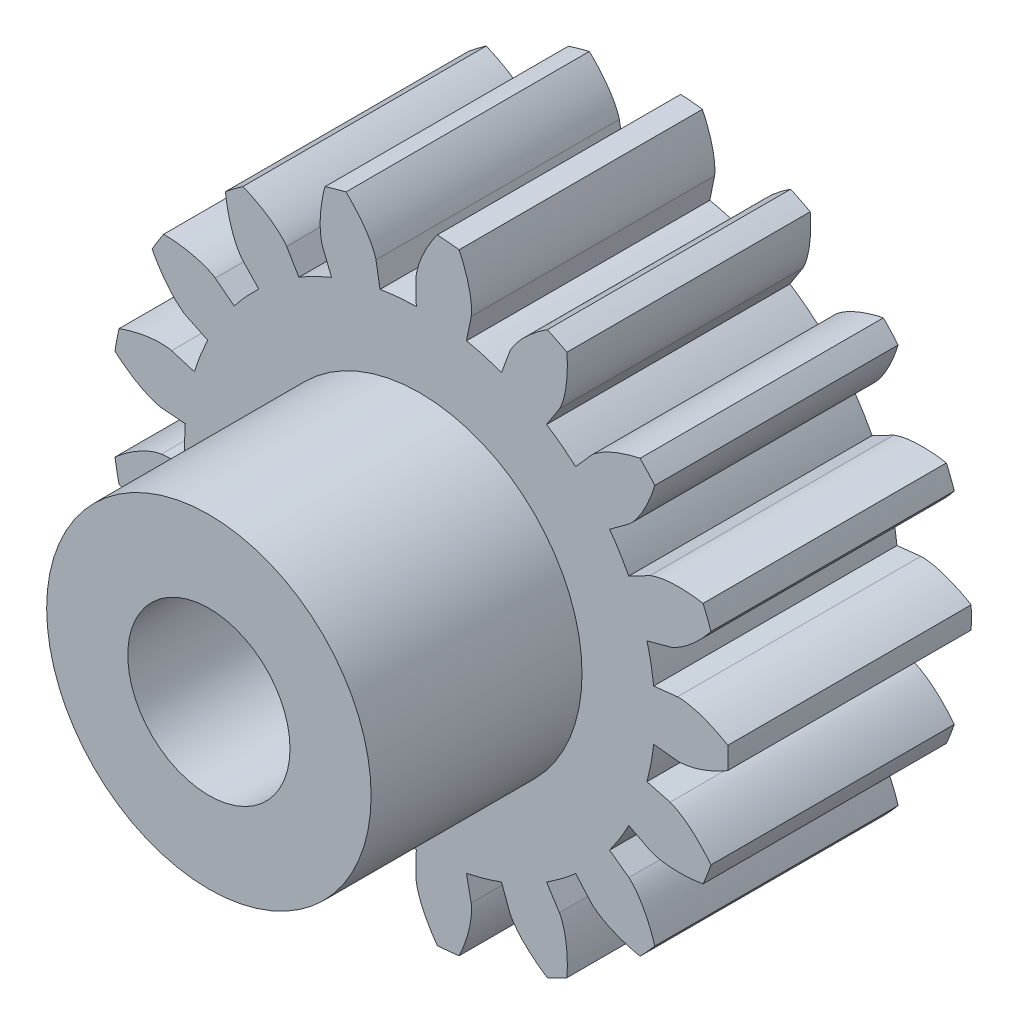
SolidWorks part; units mm, degrees
other "Kamera1"
ref_plane "Płaszczyzna przednia" through (0, 0, 0) normal (0, 0, 1) x (1, 0, 0)
ref_plane "Płaszczyzna górna" through (0, 0, 0) normal (0, 1, 0) x (1, 0, 0)
ref_plane "Płaszczyzna prawa" through (0, 0, 0) normal (1, 0, 0) x (0, 0, -1)
sketch "Szkic1" plane through (0, 0, 0) normal (0, 0, 1) x (1, 0, 0)
  circle A0 centre (0, 0) radius 9.5
extrude "Dodanie-wyciągnięcie1" add sketch "Szkic1" along normal blind 7.5
sketch "Szkic2" plane through (0, 0, 7.5) normal (0, 0, 1) x (1, 0, 0)
  circle A0 centre (0, 0) radius 5
extrude "Dodanie-wyciągnięcie2" add sketch "Szkic2" along normal blind 6.5
sketch "Szkic3" plane through (0, 0, 14) normal (0, 0, 1) x (1, 0, 0)
  circle A0 centre (0, 0) radius 2.5
extrude "Wytnij-wyciągnięcie1" cut sketch "Szkic3" against normal through all
sketch "Szkic5" plane through (0, 0, 0) normal (0, 0, -1) x (-1, 0, 0)
  line L0 (7.9634, 0.6184) -> (7.2282, 0.5613)
  line L1 (7.2282, -0.5613) -> (7.9634, -0.6184)
  line L2 (7.649, -2.3001) -> (6.9429, -2.0878)
  line L3 (6.5374, -3.1345) -> (7.2023, -3.4533)
  line L4 (6.3016, -4.9079) -> (5.7199, -4.4548)
  line L5 (4.9636, -5.2844) -> (5.4684, -5.8219)
  line L6 (4.1031, -6.8529) -> (3.7243, -6.2203)
  line L7 (2.7195, -6.7206) -> (2.9961, -7.4042)
  line L8 (1.3505, -7.8724) -> (1.2258, -7.1456)
  line L9 (0.1081, -7.2492) -> (0.119, -7.9865)
  line L10 (-1.5845, -7.8286) -> (-1.4382, -7.1059)
  line L11 (-2.518, -6.7987) -> (-2.7741, -7.4902)
  line L12 (-4.3056, -6.7276) -> (-3.9081, -6.1065)
  line L13 (-4.8039, -5.43) -> (-5.2925, -5.9823)
  line L14 (-6.4451, -4.7179) -> (-5.8501, -4.2824)
  line L15 (-6.441, -3.328) -> (-7.0962, -3.6665)
  line L16 (-7.7142, -2.0711) -> (-7.002, -1.8799)
  line L17 (-7.2083, -0.7765) -> (-7.9414, -0.8554)
  line L18 (-7.9414, 0.8554) -> (-7.2083, 0.7765)
  line L19 (-7.002, 1.8799) -> (-7.7142, 2.0711)
  line L20 (-7.0962, 3.6665) -> (-6.441, 3.328)
  line L21 (-5.8501, 4.2824) -> (-6.4451, 4.7179)
  line L22 (-5.2925, 5.9823) -> (-4.8039, 5.43)
  line L23 (-3.9081, 6.1065) -> (-4.3056, 6.7276)
  line L24 (-2.7741, 7.4902) -> (-2.518, 6.7987)
  line L25 (-1.4382, 7.1059) -> (-1.5845, 7.8286)
  line L26 (0.119, 7.9865) -> (0.1081, 7.2492)
  line L27 (1.2258, 7.1456) -> (1.3505, 7.8724)
  line L28 (2.9961, 7.4042) -> (2.7195, 6.7206)
  line L29 (3.7243, 6.2203) -> (4.1031, 6.8529)
  line L30 (5.4684, 5.8219) -> (4.9636, 5.2844)
  line L31 (5.7199, 4.4548) -> (6.3016, 4.9079)
  line L32 (7.2023, 3.4533) -> (6.5374, 3.1345)
  line L33 (6.9429, 2.0878) -> (7.649, 2.3001)
  circle A1 centre (0, 0) radius 9.5
  spline S0 degree 4 poles (7.9634, -0.6184) (7.9667, -0.6187) (7.976, -0.6197) (7.9934, -0.6223) (8.0218, -0.6274) (8.0577, -0.6353) (8.1038, -0.647) (8.1577, -0.6627) (8.2166, -0.682) (8.2801, -0.7052) (8.3429, -0.7302) (8.405, -0.757) (8.4665, -0.7852) (8.5402, -0.8212) (8.6279, -0.867) (8.7289, -0.9243) (8.8418, -0.9935) (8.9549, -1.0687) (9.0646, -1.1464) (9.1734, -1.2291) (9.2772, -1.3122) (9.3829, -1.4026) (9.4793, -1.4883) (9.5847, -1.5888) (9.669, -1.6713) (9.7774, -1.7849) (9.8406, -1.8533) (9.9135, -1.9351) (9.9453, -1.9723) (9.9649, -1.9951) knots 0 0 0 0 0 0.005377 0.015084 0.028532 0.04661 0.064855 0.092111 0.119476 0.146842 0.174209 0.201575 0.228941 0.256307 0.307035 0.361767 0.4165 0.471232 0.525964 0.580697 0.635429 0.690161 0.744894 0.799626 0.854358 0.909091 0.954545 1 1 1 1 1 construction
  spline S1 degree 4 poles (7.9634, -0.6184) (7.9667, -0.6187) (7.976, -0.6197) (7.9934, -0.6223) (8.0218, -0.6274) (8.0577, -0.6353) (8.1038, -0.647) (8.1577, -0.6627) (8.2166, -0.682) (8.2801, -0.7052) (8.3429, -0.7302) (8.405, -0.757) (8.4665, -0.7852) (8.5402, -0.8212) (8.6279, -0.867) (8.7289, -0.9243) (8.8418, -0.9935) (8.9549, -1.0687) (9.0646, -1.1464) (9.1734, -1.2291) (9.2772, -1.3122) (9.3829, -1.4026) (9.4793, -1.4883) (9.5847, -1.5888) (9.669, -1.6713) (9.7539, -1.7602) (9.7949, -1.8041) (9.8157, -1.8267) knots 0 0 0 0 0 0.005377 0.015084 0.028532 0.04661 0.064855 0.092111 0.119476 0.146842 0.174209 0.201575 0.228941 0.256307 0.307035 0.361767 0.4165 0.471232 0.525964 0.580697 0.635429 0.690161 0.744894 0.799626 0.854358 0.909091 0.909091 0.909091 0.909091 0.909091
  spline S2 degree 4 poles (7.9634, 0.6184) (7.9667, 0.6187) (7.976, 0.6197) (7.9934, 0.6223) (8.0218, 0.6274) (8.0577, 0.6353) (8.1038, 0.647) (8.1577, 0.6627) (8.2166, 0.682) (8.2801, 0.7052) (8.3429, 0.7302) (8.405, 0.757) (8.4665, 0.7852) (8.5402, 0.8212) (8.6279, 0.867) (8.7289, 0.9243) (8.8418, 0.9935) (8.9549, 1.0687) (9.0646, 1.1464) (9.1734, 1.2291) (9.2772, 1.3122) (9.3829, 1.4026) (9.4793, 1.4883) (9.5847, 1.5888) (9.669, 1.6713) (9.7774, 1.7849) (9.8406, 1.8533) (9.9135, 1.9351) (9.9453, 1.9723) (9.9649, 1.9951) knots 0 0 0 0 0 0.005377 0.015084 0.028532 0.04661 0.064855 0.092111 0.119476 0.146842 0.174209 0.201575 0.228941 0.256307 0.307035 0.361767 0.4165 0.471232 0.525964 0.580697 0.635429 0.690161 0.744894 0.799626 0.854358 0.909091 0.954545 1 1 1 1 1 construction
  spline S3 degree 4 poles (7.9634, 0.6184) (7.9667, 0.6187) (7.976, 0.6197) (7.9934, 0.6223) (8.0218, 0.6274) (8.0577, 0.6353) (8.1038, 0.647) (8.1577, 0.6627) (8.2166, 0.682) (8.2801, 0.7052) (8.3429, 0.7302) (8.405, 0.757) (8.4665, 0.7852) (8.5402, 0.8212) (8.6279, 0.867) (8.7289, 0.9243) (8.8418, 0.9935) (8.9549, 1.0687) (9.0646, 1.1464) (9.1734, 1.2291) (9.2772, 1.3122) (9.3829, 1.4026) (9.4793, 1.4883) (9.5847, 1.5888) (9.669, 1.6713) (9.7539, 1.7602) (9.7949, 1.8041) (9.8157, 1.8267) knots 0 0 0 0 0 0.005377 0.015084 0.028532 0.04661 0.064855 0.092111 0.119476 0.146842 0.174209 0.201575 0.228941 0.256307 0.307035 0.361767 0.4165 0.471232 0.525964 0.580697 0.635429 0.690161 0.744894 0.799626 0.854358 0.909091 0.909091 0.909091 0.909091 0.909091
  spline S4 degree 2 poles (7.2282, 0.5613) (7.2716, -0.0034) (7.2282, -0.5613) knots 0 0 0 0.499734 0.499734 0.499734
  spline S5 degree 2 poles (6.9429, -2.0878) (6.7793, -2.6299) (6.5374, -3.1345) knots 0 0 0 0.499734 0.499734 0.499734
  spline S6 degree 4 poles (7.2023, -3.4533) (7.2053, -3.4548) (7.2135, -3.4591) (7.2288, -3.4678) (7.2534, -3.4829) (7.284, -3.5032) (7.3228, -3.5307) (7.3675, -3.5649) (7.4154, -3.6041) (7.4662, -3.6487) (7.5157, -3.6947) (7.564, -3.7421) (7.6111, -3.7906) (7.6669, -3.8509) (7.732, -3.9252) (7.8056, -4.0151) (7.8858, -4.1205) (7.9641, -4.2314) (8.0383, -4.3435) (8.1099, -4.4599) (8.1767, -4.5749) (8.2426, -4.6974) (8.3015, -4.8121) (8.3635, -4.9439) (8.4124, -5.0513) (8.4724, -5.1963) (8.5066, -5.283) (8.545, -5.3856) (8.5612, -5.4317) (8.5713, -5.4601) knots 0 0 0 0 0 0.005377 0.015084 0.028532 0.04661 0.064855 0.092111 0.119476 0.146842 0.174209 0.201575 0.228941 0.256307 0.307035 0.361767 0.4165 0.471232 0.525964 0.580697 0.635429 0.690161 0.744894 0.799626 0.854358 0.909091 0.954545 1 1 1 1 1 construction
  spline S7 degree 4 poles (7.2023, -3.4533) (7.2053, -3.4548) (7.2135, -3.4591) (7.2288, -3.4678) (7.2534, -3.4829) (7.284, -3.5032) (7.3228, -3.5307) (7.3675, -3.5649) (7.4154, -3.6041) (7.4662, -3.6487) (7.5157, -3.6947) (7.564, -3.7421) (7.6111, -3.7906) (7.6669, -3.8509) (7.732, -3.9252) (7.8056, -4.0151) (7.8858, -4.1205) (7.9641, -4.2314) (8.0383, -4.3435) (8.1099, -4.4599) (8.1767, -4.5749) (8.2426, -4.6974) (8.3015, -4.8121) (8.3635, -4.9439) (8.4124, -5.0513) (8.4594, -5.1649) (8.4818, -5.2206) (8.493, -5.2492) knots 0 0 0 0 0 0.005377 0.015084 0.028532 0.04661 0.064855 0.092111 0.119476 0.146842 0.174209 0.201575 0.228941 0.256307 0.307035 0.361767 0.4165 0.471232 0.525964 0.580697 0.635429 0.690161 0.744894 0.799626 0.854358 0.909091 0.909091 0.909091 0.909091 0.909091
  spline S8 degree 4 poles (7.649, -2.3001) (7.6522, -2.301) (7.6612, -2.3034) (7.6784, -2.3073) (7.7067, -2.3127) (7.743, -2.3184) (7.7903, -2.3241) (7.8463, -2.329) (7.9081, -2.3322) (7.9757, -2.3335) (8.0433, -2.3329) (8.1109, -2.3304) (8.1784, -2.3263) (8.2602, -2.3193) (8.3584, -2.3083) (8.4733, -2.2914) (8.6036, -2.2676) (8.7363, -2.2383) (8.8666, -2.2055) (8.9979, -2.1677) (9.1247, -2.1278) (9.2559, -2.0816) (9.3768, -2.0365) (9.5114, -1.9809) (9.6198, -1.9344) (9.7619, -1.8677) (9.8456, -1.8266) (9.9431, -1.7767) (9.9862, -1.7536) (10.0127, -1.7393) knots 0 0 0 0 0 0.005377 0.015084 0.028532 0.04661 0.064855 0.092111 0.119476 0.146842 0.174209 0.201575 0.228941 0.256307 0.307035 0.361767 0.4165 0.471232 0.525964 0.580697 0.635429 0.690161 0.744894 0.799626 0.854358 0.909091 0.954545 1 1 1 1 1 construction
  spline S9 degree 4 poles (7.649, -2.3001) (7.6522, -2.301) (7.6612, -2.3034) (7.6784, -2.3073) (7.7067, -2.3127) (7.743, -2.3184) (7.7903, -2.3241) (7.8463, -2.329) (7.9081, -2.3322) (7.9757, -2.3335) (8.0433, -2.3329) (8.1109, -2.3304) (8.1784, -2.3263) (8.2602, -2.3193) (8.3584, -2.3083) (8.4733, -2.2914) (8.6036, -2.2676) (8.7363, -2.2383) (8.8666, -2.2055) (8.9979, -2.1677) (9.1247, -2.1278) (9.2559, -2.0816) (9.3768, -2.0365) (9.5114, -1.9809) (9.6198, -1.9344) (9.7311, -1.8822) (9.7852, -1.8561) (9.8128, -1.8425) knots 0 0 0 0 0 0.005377 0.015084 0.028532 0.04661 0.064855 0.092111 0.119476 0.146842 0.174209 0.201575 0.228941 0.256307 0.307035 0.361767 0.4165 0.471232 0.525964 0.580697 0.635429 0.690161 0.744894 0.799626 0.854358 0.909091 0.909091 0.909091 0.909091 0.909091
  spline S10 degree 2 poles (5.7199, -4.4548) (5.3715, -4.9013) (4.9636, -5.2844) knots 0 0 0 0.499734 0.499734 0.499734
  spline S11 degree 4 poles (5.4684, -5.8219) (5.4707, -5.8244) (5.4768, -5.8314) (5.488, -5.845) (5.5055, -5.8679) (5.5267, -5.8979) (5.5529, -5.9376) (5.5822, -5.9856) (5.6127, -6.0395) (5.644, -6.0994) (5.6735, -6.1602) (5.7014, -6.2218) (5.7278, -6.2841) (5.7581, -6.3604) (5.7919, -6.4533) (5.828, -6.5637) (5.8648, -6.6909) (5.8978, -6.8227) (5.9265, -6.954) (5.9511, -7.0884) (5.9719, -7.2197) (5.9891, -7.3577) (6.0026, -7.486) (6.0128, -7.6313) (6.0196, -7.7491) (6.0232, -7.906) (6.0237, -7.9992) (6.0225, -8.1087) (6.0209, -8.1576) (6.02, -8.1877) knots 0 0 0 0 0 0.005377 0.015084 0.028532 0.04661 0.064855 0.092111 0.119476 0.146842 0.174209 0.201575 0.228941 0.256307 0.307035 0.361767 0.4165 0.471232 0.525964 0.580697 0.635429 0.690161 0.744894 0.799626 0.854358 0.909091 0.954545 1 1 1 1 1 construction
  spline S12 degree 4 poles (5.4684, -5.8219) (5.4707, -5.8244) (5.4768, -5.8314) (5.488, -5.845) (5.5055, -5.8679) (5.5267, -5.8979) (5.5529, -5.9376) (5.5822, -5.9856) (5.6127, -6.0395) (5.644, -6.0994) (5.6735, -6.1602) (5.7014, -6.2218) (5.7278, -6.2841) (5.7581, -6.3604) (5.7919, -6.4533) (5.828, -6.5637) (5.8648, -6.6909) (5.8978, -6.8227) (5.9265, -6.954) (5.9511, -7.0884) (5.9719, -7.2197) (5.9891, -7.3577) (6.0026, -7.486) (6.0128, -7.6313) (6.0196, -7.7491) (6.0224, -7.872) (6.0231, -7.932) (6.0233, -7.9627) knots 0 0 0 0 0 0.005377 0.015084 0.028532 0.04661 0.064855 0.092111 0.119476 0.146842 0.174209 0.201575 0.228941 0.256307 0.307035 0.361767 0.4165 0.471232 0.525964 0.580697 0.635429 0.690161 0.744894 0.799626 0.854358 0.909091 0.909091 0.909091 0.909091 0.909091
  spline S13 degree 4 poles (6.3016, -4.9079) (6.3043, -4.9099) (6.3118, -4.9154) (6.3265, -4.9253) (6.3509, -4.9405) (6.3827, -4.9589) (6.4247, -4.9814) (6.4751, -5.0061) (6.5316, -5.0315) (6.5941, -5.0571) (6.6574, -5.0809) (6.7214, -5.103) (6.7858, -5.1235) (6.8646, -5.1466) (6.9602, -5.1718) (7.0734, -5.1976) (7.2035, -5.2224) (7.3377, -5.2431) (7.4711, -5.2596) (7.6073, -5.2717) (7.7399, -5.2803) (7.879, -5.2846) (8.0079, -5.2863) (8.1536, -5.283) (8.2714, -5.2789) (8.428, -5.268) (8.5209, -5.2599) (8.6298, -5.2486) (8.6783, -5.2426) (8.7082, -5.2389) knots 0 0 0 0 0 0.005377 0.015084 0.028532 0.04661 0.064855 0.092111 0.119476 0.146842 0.174209 0.201575 0.228941 0.256307 0.307035 0.361767 0.4165 0.471232 0.525964 0.580697 0.635429 0.690161 0.744894 0.799626 0.854358 0.909091 0.954545 1 1 1 1 1 construction
  spline S14 degree 4 poles (6.3016, -4.9079) (6.3043, -4.9099) (6.3118, -4.9154) (6.3265, -4.9253) (6.3509, -4.9405) (6.3827, -4.9589) (6.4247, -4.9814) (6.4751, -5.0061) (6.5316, -5.0315) (6.5941, -5.0571) (6.6574, -5.0809) (6.7214, -5.103) (6.7858, -5.1235) (6.8646, -5.1466) (6.9602, -5.1718) (7.0734, -5.1976) (7.2035, -5.2224) (7.3377, -5.2431) (7.4711, -5.2596) (7.6073, -5.2717) (7.7399, -5.2803) (7.879, -5.2846) (8.0079, -5.2863) (8.1536, -5.283) (8.2714, -5.2789) (8.3941, -5.2704) (8.4539, -5.2656) (8.4845, -5.2629) knots 0 0 0 0 0 0.005377 0.015084 0.028532 0.04661 0.064855 0.092111 0.119476 0.146842 0.174209 0.201575 0.228941 0.256307 0.307035 0.361767 0.4165 0.471232 0.525964 0.580697 0.635429 0.690161 0.744894 0.799626 0.854358 0.909091 0.909091 0.909091 0.909091 0.909091
  spline S15 degree 2 poles (3.7243, -6.2203) (3.2382, -6.5107) (2.7195, -6.7206) knots 0 0 0 0.499734 0.499734 0.499734
  spline S16 degree 4 poles (2.9961, -7.4042) (2.9973, -7.4073) (3.0005, -7.416) (3.0059, -7.4328) (3.014, -7.4605) (3.0229, -7.4961) (3.033, -7.5426) (3.043, -7.5979) (3.0519, -7.6592) (3.0595, -7.7263) (3.0651, -7.7937) (3.0688, -7.8613) (3.0709, -7.9288) (3.0716, -8.011) (3.0696, -8.1098) (3.0634, -8.2258) (3.0517, -8.3577) (3.0349, -8.4925) (3.0142, -8.6253) (2.9886, -8.7595) (2.9606, -8.8895) (2.9267, -9.0244) (2.893, -9.1489) (2.85, -9.2881) (2.8138, -9.4003) (2.7604, -9.548) (2.7273, -9.635) (2.6866, -9.7367) (2.6675, -9.7818) (2.6558, -9.8095) knots 0 0 0 0 0 0.005377 0.015084 0.028532 0.04661 0.064855 0.092111 0.119476 0.146842 0.174209 0.201575 0.228941 0.256307 0.307035 0.361767 0.4165 0.471232 0.525964 0.580697 0.635429 0.690161 0.744894 0.799626 0.854358 0.909091 0.954545 1 1 1 1 1 construction
  spline S17 degree 4 poles (2.9961, -7.4042) (2.9973, -7.4073) (3.0005, -7.416) (3.0059, -7.4328) (3.014, -7.4605) (3.0229, -7.4961) (3.033, -7.5426) (3.043, -7.5979) (3.0519, -7.6592) (3.0595, -7.7263) (3.0651, -7.7937) (3.0688, -7.8613) (3.0709, -7.9288) (3.0716, -8.011) (3.0696, -8.1098) (3.0634, -8.2258) (3.0517, -8.3577) (3.0349, -8.4925) (3.0142, -8.6253) (2.9886, -8.7595) (2.9606, -8.8895) (2.9267, -9.0244) (2.893, -9.1489) (2.85, -9.2881) (2.8138, -9.4003) (2.772, -9.516) (2.751, -9.5722) (2.74, -9.6009) knots 0 0 0 0 0 0.005377 0.015084 0.028532 0.04661 0.064855 0.092111 0.119476 0.146842 0.174209 0.201575 0.228941 0.256307 0.307035 0.361767 0.4165 0.471232 0.525964 0.580697 0.635429 0.690161 0.744894 0.799626 0.854358 0.909091 0.909091 0.909091 0.909091 0.909091
  spline S18 degree 4 poles (4.1031, -6.8529) (4.1049, -6.8557) (4.1099, -6.8636) (4.12, -6.878) (4.1373, -6.9011) (4.1603, -6.9297) (4.1913, -6.9658) (4.2295, -7.0071) (4.273, -7.0512) (4.322, -7.0977) (4.3724, -7.1427) (4.4241, -7.1865) (4.4767, -7.2289) (4.5419, -7.2789) (4.6219, -7.3369) (4.7182, -7.4018) (4.8305, -7.472) (4.9482, -7.5397) (5.0666, -7.6033) (5.1892, -7.6638) (5.3098, -7.7197) (5.4379, -7.774) (5.5575, -7.8221) (5.6945, -7.8717) (5.8059, -7.9104) (5.9559, -7.9568) (6.0454, -7.9828) (6.151, -8.0116) (6.1985, -8.0235) (6.2277, -8.0309) knots 0 0 0 0 0 0.005377 0.015084 0.028532 0.04661 0.064855 0.092111 0.119476 0.146842 0.174209 0.201575 0.228941 0.256307 0.307035 0.361767 0.4165 0.471232 0.525964 0.580697 0.635429 0.690161 0.744894 0.799626 0.854358 0.909091 0.954545 1 1 1 1 1 construction
  spline S19 degree 4 poles (4.1031, -6.8529) (4.1049, -6.8557) (4.1099, -6.8636) (4.12, -6.878) (4.1373, -6.9011) (4.1603, -6.9297) (4.1913, -6.9658) (4.2295, -7.0071) (4.273, -7.0512) (4.322, -7.0977) (4.3724, -7.1427) (4.4241, -7.1865) (4.4767, -7.2289) (4.5419, -7.2789) (4.6219, -7.3369) (4.7182, -7.4018) (4.8305, -7.472) (4.9482, -7.5397) (5.0666, -7.6033) (5.1892, -7.6638) (5.3098, -7.7197) (5.4379, -7.774) (5.5575, -7.8221) (5.6945, -7.8717) (5.8059, -7.9104) (5.9234, -7.9468) (5.9809, -7.9639) (6.0104, -7.9724) knots 0 0 0 0 0 0.005377 0.015084 0.028532 0.04661 0.064855 0.092111 0.119476 0.146842 0.174209 0.201575 0.228941 0.256307 0.307035 0.361767 0.4165 0.471232 0.525964 0.580697 0.635429 0.690161 0.744894 0.799626 0.854358 0.909091 0.909091 0.909091 0.909091 0.909091
  spline S20 degree 2 poles (1.2258, -7.1456) (0.6676, -7.2409) (0.1081, -7.2492) knots 0 0 0 0.499734 0.499734 0.499734
  spline S21 degree 4 poles (0.119, -7.9865) (0.119, -7.9898) (0.1189, -7.9991) (0.1179, -8.0167) (0.1154, -8.0454) (0.1109, -8.0819) (0.1035, -8.1289) (0.0928, -8.1841) (0.079, -8.2445) (0.0618, -8.3098) (0.0427, -8.3747) (0.0218, -8.439) (-0.0007, -8.5028) (-0.0297, -8.5796) (-0.0673, -8.671) (-0.1149, -8.7769) (-0.1735, -8.8957) (-0.2379, -9.0153) (-0.3051, -9.1317) (-0.3775, -9.2476) (-0.4506, -9.3587) (-0.5309, -9.4722) (-0.6073, -9.5761) (-0.6977, -9.6904) (-0.772, -9.782) (-0.8751, -9.9004) (-0.9375, -9.9696) (-1.0121, -10.0497) (-1.0462, -10.0848) (-1.0672, -10.1065) knots 0 0 0 0 0 0.005377 0.015084 0.028532 0.04661 0.064855 0.092111 0.119476 0.146842 0.174209 0.201575 0.228941 0.256307 0.307035 0.361767 0.4165 0.471232 0.525964 0.580697 0.635429 0.690161 0.744894 0.799626 0.854358 0.909091 0.954545 1 1 1 1 1 construction
  spline S22 degree 4 poles (0.119, -7.9865) (0.119, -7.9898) (0.1189, -7.9991) (0.1179, -8.0167) (0.1154, -8.0454) (0.1109, -8.0819) (0.1035, -8.1289) (0.0928, -8.1841) (0.079, -8.2445) (0.0618, -8.3098) (0.0427, -8.3747) (0.0218, -8.439) (-0.0007, -8.5028) (-0.0297, -8.5796) (-0.0673, -8.671) (-0.1149, -8.7769) (-0.1735, -8.8957) (-0.2379, -9.0153) (-0.3051, -9.1317) (-0.3775, -9.2476) (-0.4506, -9.3587) (-0.5309, -9.4722) (-0.6073, -9.5761) (-0.6977, -9.6904) (-0.772, -9.782) (-0.8527, -9.8747) (-0.8926, -9.9196) (-0.9132, -9.9424) knots 0 0 0 0 0 0.005377 0.015084 0.028532 0.04661 0.064855 0.092111 0.119476 0.146842 0.174209 0.201575 0.228941 0.256307 0.307035 0.361767 0.4165 0.471232 0.525964 0.580697 0.635429 0.690161 0.744894 0.799626 0.854358 0.909091 0.909091 0.909091 0.909091 0.909091
  spline S23 degree 4 poles (1.3505, -7.8724) (1.3511, -7.8757) (1.353, -7.8848) (1.3572, -7.9019) (1.3649, -7.9296) (1.3761, -7.9647) (1.392, -8.0095) (1.4126, -8.0618) (1.4372, -8.1186) (1.4662, -8.1797) (1.4969, -8.2399) (1.5293, -8.2993) (1.563, -8.3579) (1.6057, -8.428) (1.6594, -8.511) (1.7257, -8.6064) (1.8051, -8.7124) (1.8904, -8.8181) (1.9779, -8.9201) (2.0703, -9.0208) (2.1626, -9.1166) (2.2624, -9.2134) (2.3566, -9.3015) (2.4664, -9.3972) (2.5563, -9.4736) (2.6794, -9.571) (2.7534, -9.6276) (2.8415, -9.6926) (2.8815, -9.7209) (2.906, -9.7383) knots 0 0 0 0 0 0.005377 0.015084 0.028532 0.04661 0.064855 0.092111 0.119476 0.146842 0.174209 0.201575 0.228941 0.256307 0.307035 0.361767 0.4165 0.471232 0.525964 0.580697 0.635429 0.690161 0.744894 0.799626 0.854358 0.909091 0.954545 1 1 1 1 1 construction
  spline S24 degree 4 poles (1.3505, -7.8724) (1.3511, -7.8757) (1.353, -7.8848) (1.3572, -7.9019) (1.3649, -7.9296) (1.3761, -7.9647) (1.392, -8.0095) (1.4126, -8.0618) (1.4372, -8.1186) (1.4662, -8.1797) (1.4969, -8.2399) (1.5293, -8.2993) (1.563, -8.3579) (1.6057, -8.428) (1.6594, -8.511) (1.7257, -8.6064) (1.8051, -8.7124) (1.8904, -8.8181) (1.9779, -8.9201) (2.0703, -9.0208) (2.1626, -9.1166) (2.2624, -9.2134) (2.3566, -9.3015) (2.4664, -9.3972) (2.5563, -9.4736) (2.6527, -9.5499) (2.7001, -9.5867) (2.7246, -9.6053) knots 0 0 0 0 0 0.005377 0.015084 0.028532 0.04661 0.064855 0.092111 0.119476 0.146842 0.174209 0.201575 0.228941 0.256307 0.307035 0.361767 0.4165 0.471232 0.525964 0.580697 0.635429 0.690161 0.744894 0.799626 0.854358 0.909091 0.909091 0.909091 0.909091 0.909091
  spline S25 degree 2 poles (-1.4382, -7.1059) (-1.9932, -6.9931) (-2.518, -6.7987) knots 0 0 0 0.499734 0.499734 0.499734
  spline S26 degree 4 poles (-2.7741, -7.4902) (-2.7753, -7.4933) (-2.7788, -7.5019) (-2.786, -7.518) (-2.7987, -7.5438) (-2.8161, -7.5762) (-2.84, -7.6174) (-2.8699, -7.665) (-2.9046, -7.7163) (-2.9442, -7.771) (-2.9855, -7.8246) (-3.0282, -7.877) (-3.0722, -7.9284) (-3.127, -7.9895) (-3.1951, -8.0612) (-3.2778, -8.1427) (-3.3753, -8.2324) (-3.4785, -8.3206) (-3.5833, -8.4048) (-3.6926, -8.4868) (-3.8009, -8.564) (-3.9168, -8.6408) (-4.0256, -8.7101) (-4.1511, -8.784) (-4.2536, -8.8426) (-4.3924, -8.9157) (-4.4756, -8.9577) (-4.5742, -9.0054) (-4.6186, -9.0259) (-4.646, -9.0385) knots 0 0 0 0 0 0.005377 0.015084 0.028532 0.04661 0.064855 0.092111 0.119476 0.146842 0.174209 0.201575 0.228941 0.256307 0.307035 0.361767 0.4165 0.471232 0.525964 0.580697 0.635429 0.690161 0.744894 0.799626 0.854358 0.909091 0.954545 1 1 1 1 1 construction
  spline S27 degree 4 poles (-2.7741, -7.4902) (-2.7753, -7.4933) (-2.7788, -7.5019) (-2.786, -7.518) (-2.7987, -7.5438) (-2.8161, -7.5762) (-2.84, -7.6174) (-2.8699, -7.665) (-2.9046, -7.7163) (-2.9442, -7.771) (-2.9855, -7.8246) (-3.0282, -7.877) (-3.0722, -7.9284) (-3.127, -7.9895) (-3.1951, -8.0612) (-3.2778, -8.1427) (-3.3753, -8.2324) (-3.4785, -8.3206) (-3.5833, -8.4048) (-3.6926, -8.4868) (-3.8009, -8.564) (-3.9168, -8.6408) (-4.0256, -8.7101) (-4.1511, -8.784) (-4.2536, -8.8426) (-4.3623, -8.8999) (-4.4157, -8.9273) (-4.4432, -8.9411) knots 0 0 0 0 0 0.005377 0.015084 0.028532 0.04661 0.064855 0.092111 0.119476 0.146842 0.174209 0.201575 0.228941 0.256307 0.307035 0.361767 0.4165 0.471232 0.525964 0.580697 0.635429 0.690161 0.744894 0.799626 0.854358 0.909091 0.909091 0.909091 0.909091 0.909091
  spline S28 degree 4 poles (-1.5845, -7.8286) (-1.5851, -7.8319) (-1.5867, -7.8411) (-1.589, -7.8586) (-1.5918, -7.8872) (-1.594, -7.9239) (-1.5954, -7.9715) (-1.5951, -8.0277) (-1.5926, -8.0896) (-1.5877, -8.157) (-1.5808, -8.2242) (-1.5721, -8.2913) (-1.5617, -8.3581) (-1.5473, -8.439) (-1.5272, -8.5358) (-1.4998, -8.6486) (-1.4641, -8.7761) (-1.4227, -8.9055) (-1.378, -9.0323) (-1.3282, -9.1595) (-1.2768, -9.2821) (-1.2187, -9.4085) (-1.1627, -9.5247) (-1.0948, -9.6536) (-1.0386, -9.7573) (-0.959, -9.8926) (-0.9104, -9.9721) (-0.8517, -10.0646) (-0.8247, -10.1054) (-0.8081, -10.1305) knots 0 0 0 0 0 0.005377 0.015084 0.028532 0.04661 0.064855 0.092111 0.119476 0.146842 0.174209 0.201575 0.228941 0.256307 0.307035 0.361767 0.4165 0.471232 0.525964 0.580697 0.635429 0.690161 0.744894 0.799626 0.854358 0.909091 0.954545 1 1 1 1 1 construction
  spline S29 degree 4 poles (-1.5845, -7.8286) (-1.5851, -7.8319) (-1.5867, -7.8411) (-1.589, -7.8586) (-1.5918, -7.8872) (-1.594, -7.9239) (-1.5954, -7.9715) (-1.5951, -8.0277) (-1.5926, -8.0896) (-1.5877, -8.157) (-1.5808, -8.2242) (-1.5721, -8.2913) (-1.5617, -8.3581) (-1.5473, -8.439) (-1.5272, -8.5358) (-1.4998, -8.6486) (-1.4641, -8.7761) (-1.4227, -8.9055) (-1.378, -9.0323) (-1.3282, -9.1595) (-1.2768, -9.2821) (-1.2187, -9.4085) (-1.1627, -9.5247) (-1.0948, -9.6536) (-1.0386, -9.7573) (-0.9763, -9.8633) (-0.9453, -9.9147) (-0.9292, -9.9409) knots 0 0 0 0 0 0.005377 0.015084 0.028532 0.04661 0.064855 0.092111 0.119476 0.146842 0.174209 0.201575 0.228941 0.256307 0.307035 0.361767 0.4165 0.471232 0.525964 0.580697 0.635429 0.690161 0.744894 0.799626 0.854358 0.909091 0.909091 0.909091 0.909091 0.909091
  spline S30 degree 2 poles (-3.9081, -6.1065) (-4.3848, -5.8008) (-4.8039, -5.43) knots 0 0 0 0.499734 0.499734 0.499734
  spline S31 degree 4 poles (-5.2925, -5.9823) (-5.2947, -5.9847) (-5.3011, -5.9915) (-5.3137, -6.0039) (-5.3349, -6.0234) (-5.3628, -6.0473) (-5.3999, -6.0771) (-5.445, -6.1106) (-5.4959, -6.146) (-5.5526, -6.1827) (-5.6104, -6.2177) (-5.6692, -6.2512) (-5.7288, -6.2832) (-5.802, -6.3204) (-5.8914, -6.3627) (-5.9979, -6.4088) (-6.1212, -6.4572) (-6.2494, -6.5021) (-6.3775, -6.5428) (-6.5091, -6.5798) (-6.6379, -6.6126) (-6.7738, -6.6424) (-6.9002, -6.6677) (-7.044, -6.6913) (-7.1606, -6.7089) (-7.3166, -6.7269) (-7.4093, -6.7361) (-7.5184, -6.7449) (-7.5673, -6.7479) (-7.5973, -6.7498) knots 0 0 0 0 0 0.005377 0.015084 0.028532 0.04661 0.064855 0.092111 0.119476 0.146842 0.174209 0.201575 0.228941 0.256307 0.307035 0.361767 0.4165 0.471232 0.525964 0.580697 0.635429 0.690161 0.744894 0.799626 0.854358 0.909091 0.954545 1 1 1 1 1 construction
  spline S32 degree 4 poles (-5.2925, -5.9823) (-5.2947, -5.9847) (-5.3011, -5.9915) (-5.3137, -6.0039) (-5.3349, -6.0234) (-5.3628, -6.0473) (-5.3999, -6.0771) (-5.445, -6.1106) (-5.4959, -6.146) (-5.5526, -6.1827) (-5.6104, -6.2177) (-5.6692, -6.2512) (-5.7288, -6.2832) (-5.802, -6.3204) (-5.8914, -6.3627) (-5.9979, -6.4088) (-6.1212, -6.4572) (-6.2494, -6.5021) (-6.3775, -6.5428) (-6.5091, -6.5798) (-6.6379, -6.6126) (-6.7738, -6.6424) (-6.9002, -6.6677) (-7.044, -6.6913) (-7.1606, -6.7089) (-7.2827, -6.723) (-7.3424, -6.7293) (-7.373, -6.7323) knots 0 0 0 0 0 0.005377 0.015084 0.028532 0.04661 0.064855 0.092111 0.119476 0.146842 0.174209 0.201575 0.228941 0.256307 0.307035 0.361767 0.4165 0.471232 0.525964 0.580697 0.635429 0.690161 0.744894 0.799626 0.854358 0.909091 0.909091 0.909091 0.909091 0.909091
  spline S33 degree 4 poles (-4.3056, -6.7276) (-4.3073, -6.7304) (-4.3121, -6.7384) (-4.3205, -6.7539) (-4.3335, -6.7796) (-4.3488, -6.813) (-4.3673, -6.8569) (-4.3873, -6.9094) (-4.4073, -6.968) (-4.4271, -7.0326) (-4.445, -7.0978) (-4.4611, -7.1635) (-4.4756, -7.2296) (-4.4913, -7.3102) (-4.5075, -7.4077) (-4.5227, -7.5228) (-4.5355, -7.6546) (-4.5437, -7.7902) (-4.5478, -7.9245) (-4.5473, -8.0612) (-4.5436, -8.1941) (-4.5351, -8.3329) (-4.5249, -8.4615) (-4.5082, -8.6062) (-4.4932, -8.7232) (-4.4679, -8.8782) (-4.4513, -8.9698) (-4.4299, -9.0773) (-4.4195, -9.125) (-4.413, -9.1545) knots 0 0 0 0 0 0.005377 0.015084 0.028532 0.04661 0.064855 0.092111 0.119476 0.146842 0.174209 0.201575 0.228941 0.256307 0.307035 0.361767 0.4165 0.471232 0.525964 0.580697 0.635429 0.690161 0.744894 0.799626 0.854358 0.909091 0.954545 1 1 1 1 1 construction
  spline S34 degree 4 poles (-4.3056, -6.7276) (-4.3073, -6.7304) (-4.3121, -6.7384) (-4.3205, -6.7539) (-4.3335, -6.7796) (-4.3488, -6.813) (-4.3673, -6.8569) (-4.3873, -6.9094) (-4.4073, -6.968) (-4.4271, -7.0326) (-4.445, -7.0978) (-4.4611, -7.1635) (-4.4756, -7.2296) (-4.4913, -7.3102) (-4.5075, -7.4077) (-4.5227, -7.5228) (-4.5355, -7.6546) (-4.5437, -7.7902) (-4.5478, -7.9245) (-4.5473, -8.0612) (-4.5436, -8.1941) (-4.5351, -8.3329) (-4.5249, -8.4615) (-4.5082, -8.6062) (-4.4932, -8.7232) (-4.4734, -8.8446) (-4.4631, -8.9037) (-4.4576, -8.9339) knots 0 0 0 0 0 0.005377 0.015084 0.028532 0.04661 0.064855 0.092111 0.119476 0.146842 0.174209 0.201575 0.228941 0.256307 0.307035 0.361767 0.4165 0.471232 0.525964 0.580697 0.635429 0.690161 0.744894 0.799626 0.854358 0.909091 0.909091 0.909091 0.909091 0.909091
  spline S35 degree 2 poles (-5.8501, -4.2824) (-6.1842, -3.8251) (-6.441, -3.328) knots 0 0 0 0.499734 0.499734 0.499734
  spline S36 degree 4 poles (-7.0962, -3.6665) (-7.0991, -3.6679) (-7.1076, -3.6719) (-7.1237, -3.6789) (-7.1505, -3.6895) (-7.1852, -3.7017) (-7.2306, -3.716) (-7.2847, -3.731) (-7.3449, -3.7456) (-7.4111, -3.7593) (-7.4777, -3.7711) (-7.5446, -3.7811) (-7.6117, -3.7894) (-7.6934, -3.7976) (-7.792, -3.8048) (-7.908, -3.8093) (-8.0405, -3.8099) (-8.1762, -3.8055) (-8.3104, -3.7972) (-8.4464, -3.7841) (-8.5784, -3.7682) (-8.7158, -3.7469) (-8.8429, -3.7248) (-8.9855, -3.6949) (-9.1006, -3.6691) (-9.2525, -3.6296) (-9.3423, -3.6047) (-9.4473, -3.5735) (-9.4939, -3.5587) (-9.5226, -3.5496) knots 0 0 0 0 0 0.005377 0.015084 0.028532 0.04661 0.064855 0.092111 0.119476 0.146842 0.174209 0.201575 0.228941 0.256307 0.307035 0.361767 0.4165 0.471232 0.525964 0.580697 0.635429 0.690161 0.744894 0.799626 0.854358 0.909091 0.954545 1 1 1 1 1 construction
  spline S37 degree 4 poles (-7.0962, -3.6665) (-7.0991, -3.6679) (-7.1076, -3.6719) (-7.1237, -3.6789) (-7.1505, -3.6895) (-7.1852, -3.7017) (-7.2306, -3.716) (-7.2847, -3.731) (-7.3449, -3.7456) (-7.4111, -3.7593) (-7.4777, -3.7711) (-7.5446, -3.7811) (-7.6117, -3.7894) (-7.6934, -3.7976) (-7.792, -3.8048) (-7.908, -3.8093) (-8.0405, -3.8099) (-8.1762, -3.8055) (-8.3104, -3.7972) (-8.4464, -3.7841) (-8.5784, -3.7682) (-8.7158, -3.7469) (-8.8429, -3.7248) (-8.9855, -3.6949) (-9.1006, -3.6691) (-9.2196, -3.6382) (-9.2775, -3.6225) (-9.3071, -3.6142) knots 0 0 0 0 0 0.005377 0.015084 0.028532 0.04661 0.064855 0.092111 0.119476 0.146842 0.174209 0.201575 0.228941 0.256307 0.307035 0.361767 0.4165 0.471232 0.525964 0.580697 0.635429 0.690161 0.744894 0.799626 0.854358 0.909091 0.909091 0.909091 0.909091 0.909091
  spline S38 degree 4 poles (-6.4451, -4.7179) (-6.4478, -4.7199) (-6.4551, -4.7257) (-6.4685, -4.7371) (-6.4899, -4.7564) (-6.5163, -4.782) (-6.5494, -4.8162) (-6.587, -4.858) (-6.6268, -4.9053) (-6.6686, -4.9585) (-6.7088, -5.0128) (-6.7476, -5.0683) (-6.785, -5.1246) (-6.8287, -5.1941) (-6.8791, -5.2791) (-6.9349, -5.381) (-6.9944, -5.4993) (-7.051, -5.6228) (-7.1033, -5.7466) (-7.1523, -5.8742) (-7.1969, -5.9994) (-7.2391, -6.132) (-7.276, -6.2555) (-7.3127, -6.3965) (-7.341, -6.5111) (-7.3733, -6.6647) (-7.391, -6.7561) (-7.4099, -6.864) (-7.4174, -6.9124) (-7.422, -6.9421) knots 0 0 0 0 0 0.005377 0.015084 0.028532 0.04661 0.064855 0.092111 0.119476 0.146842 0.174209 0.201575 0.228941 0.256307 0.307035 0.361767 0.4165 0.471232 0.525964 0.580697 0.635429 0.690161 0.744894 0.799626 0.854358 0.909091 0.954545 1 1 1 1 1 construction
  spline S39 degree 4 poles (-6.4451, -4.7179) (-6.4478, -4.7199) (-6.4551, -4.7257) (-6.4685, -4.7371) (-6.4899, -4.7564) (-6.5163, -4.782) (-6.5494, -4.8162) (-6.587, -4.858) (-6.6268, -4.9053) (-6.6686, -4.9585) (-6.7088, -5.0128) (-6.7476, -5.0683) (-6.785, -5.1246) (-6.8287, -5.1941) (-6.8791, -5.2791) (-6.9349, -5.381) (-6.9944, -5.4993) (-7.051, -5.6228) (-7.1033, -5.7466) (-7.1523, -5.8742) (-7.1969, -5.9994) (-7.2391, -6.132) (-7.276, -6.2555) (-7.3127, -6.3965) (-7.341, -6.5111) (-7.3663, -6.6314) (-7.3781, -6.6902) (-7.3839, -6.7204) knots 0 0 0 0 0 0.005377 0.015084 0.028532 0.04661 0.064855 0.092111 0.119476 0.146842 0.174209 0.201575 0.228941 0.256307 0.307035 0.361767 0.4165 0.471232 0.525964 0.580697 0.635429 0.690161 0.744894 0.799626 0.854358 0.909091 0.909091 0.909091 0.909091 0.909091
  spline S40 degree 2 poles (-7.002, -1.8799) (-7.1484, -1.3328) (-7.2083, -0.7765) knots 0 0 0 0.499734 0.499734 0.499734
  spline S41 degree 4 poles (-7.9414, -0.8554) (-7.9448, -0.8557) (-7.954, -0.8564) (-7.9717, -0.8571) (-8.0005, -0.8572) (-8.0372, -0.8561) (-8.0847, -0.8531) (-8.1406, -0.8475) (-8.202, -0.8394) (-8.2687, -0.8283) (-8.335, -0.8152) (-8.401, -0.8003) (-8.4666, -0.7839) (-8.5457, -0.762) (-8.6403, -0.7331) (-8.7501, -0.6954) (-8.8738, -0.648) (-8.9988, -0.5949) (-9.1209, -0.5387) (-9.243, -0.4774) (-9.3604, -0.4149) (-9.4808, -0.3454) (-9.5913, -0.2789) (-9.7134, -0.1994) (-9.8115, -0.1338) (-9.9389, -0.0421) (-10.0136, 0.0136) (-10.1002, 0.0806) (-10.1383, 0.1112) (-10.1618, 0.1301) knots 0 0 0 0 0 0.005377 0.015084 0.028532 0.04661 0.064855 0.092111 0.119476 0.146842 0.174209 0.201575 0.228941 0.256307 0.307035 0.361767 0.4165 0.471232 0.525964 0.580697 0.635429 0.690161 0.744894 0.799626 0.854358 0.909091 0.954545 1 1 1 1 1 construction
  spline S42 degree 4 poles (-7.9414, -0.8554) (-7.9448, -0.8557) (-7.954, -0.8564) (-7.9717, -0.8571) (-8.0005, -0.8572) (-8.0372, -0.8561) (-8.0847, -0.8531) (-8.1406, -0.8475) (-8.202, -0.8394) (-8.2687, -0.8283) (-8.335, -0.8152) (-8.401, -0.8003) (-8.4666, -0.7839) (-8.5457, -0.762) (-8.6403, -0.7331) (-8.7501, -0.6954) (-8.8738, -0.648) (-8.9988, -0.5949) (-9.1209, -0.5387) (-9.243, -0.4774) (-9.3604, -0.4149) (-9.4808, -0.3454) (-9.5913, -0.2789) (-9.7134, -0.1994) (-9.8115, -0.1338) (-9.9113, -0.062) (-9.9596, -0.0265) (-9.9842, -0.008) knots 0 0 0 0 0 0.005377 0.015084 0.028532 0.04661 0.064855 0.092111 0.119476 0.146842 0.174209 0.201575 0.228941 0.256307 0.307035 0.361767 0.4165 0.471232 0.525964 0.580697 0.635429 0.690161 0.744894 0.799626 0.854358 0.909091 0.909091 0.909091 0.909091 0.909091
  spline S43 degree 4 poles (-7.7142, -2.0711) (-7.7174, -2.072) (-7.7263, -2.0747) (-7.743, -2.0805) (-7.7699, -2.0907) (-7.8037, -2.1051) (-7.8469, -2.125) (-7.8971, -2.1504) (-7.9514, -2.1802) (-8.0095, -2.2147) (-8.0666, -2.2508) (-8.1228, -2.2885) (-8.178, -2.3275) (-8.2439, -2.3765) (-8.3216, -2.4376) (-8.4104, -2.5125) (-8.5087, -2.6013) (-8.606, -2.696) (-8.6996, -2.7925) (-8.7913, -2.8938) (-8.8781, -2.9945) (-8.9654, -3.1028) (-9.0444, -3.2047) (-9.1296, -3.3229) (-9.1973, -3.4195) (-9.283, -3.5511) (-9.3325, -3.63) (-9.3891, -3.7237) (-9.4135, -3.7661) (-9.4286, -3.7922) knots 0 0 0 0 0 0.005377 0.015084 0.028532 0.04661 0.064855 0.092111 0.119476 0.146842 0.174209 0.201575 0.228941 0.256307 0.307035 0.361767 0.4165 0.471232 0.525964 0.580697 0.635429 0.690161 0.744894 0.799626 0.854358 0.909091 0.954545 1 1 1 1 1 construction
  spline S44 degree 4 poles (-7.7142, -2.0711) (-7.7174, -2.072) (-7.7263, -2.0747) (-7.743, -2.0805) (-7.7699, -2.0907) (-7.8037, -2.1051) (-7.8469, -2.125) (-7.8971, -2.1504) (-7.9514, -2.1802) (-8.0095, -2.2147) (-8.0666, -2.2508) (-8.1228, -2.2885) (-8.178, -2.3275) (-8.2439, -2.3765) (-8.3216, -2.4376) (-8.4104, -2.5125) (-8.5087, -2.6013) (-8.606, -2.696) (-8.6996, -2.7925) (-8.7913, -2.8938) (-8.8781, -2.9945) (-8.9654, -3.1028) (-9.0444, -3.2047) (-9.1296, -3.3229) (-9.1973, -3.4195) (-9.2644, -3.5225) (-9.2966, -3.5732) (-9.3129, -3.5992) knots 0 0 0 0 0 0.005377 0.015084 0.028532 0.04661 0.064855 0.092111 0.119476 0.146842 0.174209 0.201575 0.228941 0.256307 0.307035 0.361767 0.4165 0.471232 0.525964 0.580697 0.635429 0.690161 0.744894 0.799626 0.854358 0.909091 0.909091 0.909091 0.909091 0.909091
  spline S45 degree 2 poles (-7.2083, 0.7765) (-7.1471, 1.3395) (-7.002, 1.8799) knots 0 0 0 0.499734 0.499734 0.499734
  spline S46 degree 4 poles (-7.7142, 2.0711) (-7.7174, 2.072) (-7.7263, 2.0747) (-7.743, 2.0805) (-7.7699, 2.0907) (-7.8037, 2.1051) (-7.8469, 2.125) (-7.8971, 2.1504) (-7.9514, 2.1802) (-8.0095, 2.2147) (-8.0666, 2.2508) (-8.1228, 2.2885) (-8.178, 2.3275) (-8.2439, 2.3765) (-8.3216, 2.4376) (-8.4104, 2.5125) (-8.5087, 2.6013) (-8.606, 2.696) (-8.6996, 2.7925) (-8.7913, 2.8938) (-8.8781, 2.9945) (-8.9654, 3.1028) (-9.0444, 3.2047) (-9.1296, 3.3229) (-9.1973, 3.4195) (-9.283, 3.5511) (-9.3325, 3.63) (-9.3891, 3.7237) (-9.4135, 3.7661) (-9.4286, 3.7922) knots 0 0 0 0 0 0.005377 0.015084 0.028532 0.04661 0.064855 0.092111 0.119476 0.146842 0.174209 0.201575 0.228941 0.256307 0.307035 0.361767 0.4165 0.471232 0.525964 0.580697 0.635429 0.690161 0.744894 0.799626 0.854358 0.909091 0.954545 1 1 1 1 1 construction
  spline S47 degree 4 poles (-7.7142, 2.0711) (-7.7174, 2.072) (-7.7263, 2.0747) (-7.743, 2.0805) (-7.7699, 2.0907) (-7.8037, 2.1051) (-7.8469, 2.125) (-7.8971, 2.1504) (-7.9514, 2.1802) (-8.0095, 2.2147) (-8.0666, 2.2508) (-8.1228, 2.2885) (-8.178, 2.3275) (-8.2439, 2.3765) (-8.3216, 2.4376) (-8.4104, 2.5125) (-8.5087, 2.6013) (-8.606, 2.696) (-8.6996, 2.7925) (-8.7913, 2.8938) (-8.8781, 2.9945) (-8.9654, 3.1028) (-9.0444, 3.2047) (-9.1296, 3.3229) (-9.1973, 3.4195) (-9.2644, 3.5225) (-9.2966, 3.5732) (-9.3129, 3.5992) knots 0 0 0 0 0 0.005377 0.015084 0.028532 0.04661 0.064855 0.092111 0.119476 0.146842 0.174209 0.201575 0.228941 0.256307 0.307035 0.361767 0.4165 0.471232 0.525964 0.580697 0.635429 0.690161 0.744894 0.799626 0.854358 0.909091 0.909091 0.909091 0.909091 0.909091
  spline S48 degree 4 poles (-7.9414, 0.8554) (-7.9448, 0.8557) (-7.954, 0.8564) (-7.9717, 0.8571) (-8.0005, 0.8572) (-8.0372, 0.8561) (-8.0847, 0.8531) (-8.1406, 0.8475) (-8.202, 0.8394) (-8.2687, 0.8283) (-8.335, 0.8152) (-8.401, 0.8003) (-8.4666, 0.7839) (-8.5457, 0.762) (-8.6403, 0.7331) (-8.7501, 0.6954) (-8.8738, 0.648) (-8.9988, 0.5949) (-9.1209, 0.5387) (-9.243, 0.4774) (-9.3604, 0.4149) (-9.4808, 0.3454) (-9.5913, 0.2789) (-9.7134, 0.1994) (-9.8115, 0.1338) (-9.9389, 0.0421) (-10.0136, -0.0136) (-10.1002, -0.0806) (-10.1383, -0.1112) (-10.1618, -0.1301) knots 0 0 0 0 0 0.005377 0.015084 0.028532 0.04661 0.064855 0.092111 0.119476 0.146842 0.174209 0.201575 0.228941 0.256307 0.307035 0.361767 0.4165 0.471232 0.525964 0.580697 0.635429 0.690161 0.744894 0.799626 0.854358 0.909091 0.954545 1 1 1 1 1 construction
  spline S49 degree 4 poles (-7.9414, 0.8554) (-7.9448, 0.8557) (-7.954, 0.8564) (-7.9717, 0.8571) (-8.0005, 0.8572) (-8.0372, 0.8561) (-8.0847, 0.8531) (-8.1406, 0.8475) (-8.202, 0.8394) (-8.2687, 0.8283) (-8.335, 0.8152) (-8.401, 0.8003) (-8.4666, 0.7839) (-8.5457, 0.762) (-8.6403, 0.7331) (-8.7501, 0.6954) (-8.8738, 0.648) (-8.9988, 0.5949) (-9.1209, 0.5387) (-9.243, 0.4774) (-9.3604, 0.4149) (-9.4808, 0.3454) (-9.5913, 0.2789) (-9.7134, 0.1994) (-9.8115, 0.1338) (-9.9113, 0.062) (-9.9596, 0.0265) (-9.9842, 0.008) knots 0 0 0 0 0 0.005377 0.015084 0.028532 0.04661 0.064855 0.092111 0.119476 0.146842 0.174209 0.201575 0.228941 0.256307 0.307035 0.361767 0.4165 0.471232 0.525964 0.580697 0.635429 0.690161 0.744894 0.799626 0.854358 0.909091 0.909091 0.909091 0.909091 0.909091
  spline S50 degree 2 poles (-6.441, 3.328) (-6.1806, 3.8308) (-5.8501, 4.2824) knots 0 0 0 0.499734 0.499734 0.499734
  spline S51 degree 4 poles (-6.4451, 4.7179) (-6.4478, 4.7199) (-6.4551, 4.7257) (-6.4685, 4.7371) (-6.4899, 4.7564) (-6.5163, 4.782) (-6.5494, 4.8162) (-6.587, 4.858) (-6.6268, 4.9053) (-6.6686, 4.9585) (-6.7088, 5.0128) (-6.7476, 5.0683) (-6.785, 5.1246) (-6.8287, 5.1941) (-6.8791, 5.2791) (-6.9349, 5.381) (-6.9944, 5.4993) (-7.051, 5.6228) (-7.1033, 5.7466) (-7.1523, 5.8742) (-7.1969, 5.9994) (-7.2391, 6.132) (-7.276, 6.2555) (-7.3127, 6.3965) (-7.341, 6.5111) (-7.3733, 6.6647) (-7.391, 6.7561) (-7.4099, 6.864) (-7.4174, 6.9124) (-7.422, 6.9421) knots 0 0 0 0 0 0.005377 0.015084 0.028532 0.04661 0.064855 0.092111 0.119476 0.146842 0.174209 0.201575 0.228941 0.256307 0.307035 0.361767 0.4165 0.471232 0.525964 0.580697 0.635429 0.690161 0.744894 0.799626 0.854358 0.909091 0.954545 1 1 1 1 1 construction
  spline S52 degree 4 poles (-6.4451, 4.7179) (-6.4478, 4.7199) (-6.4551, 4.7257) (-6.4685, 4.7371) (-6.4899, 4.7564) (-6.5163, 4.782) (-6.5494, 4.8162) (-6.587, 4.858) (-6.6268, 4.9053) (-6.6686, 4.9585) (-6.7088, 5.0128) (-6.7476, 5.0683) (-6.785, 5.1246) (-6.8287, 5.1941) (-6.8791, 5.2791) (-6.9349, 5.381) (-6.9944, 5.4993) (-7.051, 5.6228) (-7.1033, 5.7466) (-7.1523, 5.8742) (-7.1969, 5.9994) (-7.2391, 6.132) (-7.276, 6.2555) (-7.3127, 6.3965) (-7.341, 6.5111) (-7.3663, 6.6314) (-7.3781, 6.6902) (-7.3839, 6.7204) knots 0 0 0 0 0 0.005377 0.015084 0.028532 0.04661 0.064855 0.092111 0.119476 0.146842 0.174209 0.201575 0.228941 0.256307 0.307035 0.361767 0.4165 0.471232 0.525964 0.580697 0.635429 0.690161 0.744894 0.799626 0.854358 0.909091 0.909091 0.909091 0.909091 0.909091
  spline S53 degree 4 poles (-7.0962, 3.6665) (-7.0991, 3.6679) (-7.1076, 3.6719) (-7.1237, 3.6789) (-7.1505, 3.6895) (-7.1852, 3.7017) (-7.2306, 3.716) (-7.2847, 3.731) (-7.3449, 3.7456) (-7.4111, 3.7593) (-7.4777, 3.7711) (-7.5446, 3.7811) (-7.6117, 3.7894) (-7.6934, 3.7976) (-7.792, 3.8048) (-7.908, 3.8093) (-8.0405, 3.8099) (-8.1762, 3.8055) (-8.3104, 3.7972) (-8.4464, 3.7841) (-8.5784, 3.7682) (-8.7158, 3.7469) (-8.8429, 3.7248) (-8.9855, 3.6949) (-9.1006, 3.6691) (-9.2525, 3.6296) (-9.3423, 3.6047) (-9.4473, 3.5735) (-9.4939, 3.5587) (-9.5226, 3.5496) knots 0 0 0 0 0 0.005377 0.015084 0.028532 0.04661 0.064855 0.092111 0.119476 0.146842 0.174209 0.201575 0.228941 0.256307 0.307035 0.361767 0.4165 0.471232 0.525964 0.580697 0.635429 0.690161 0.744894 0.799626 0.854358 0.909091 0.954545 1 1 1 1 1 construction
  spline S54 degree 4 poles (-7.0962, 3.6665) (-7.0991, 3.6679) (-7.1076, 3.6719) (-7.1237, 3.6789) (-7.1505, 3.6895) (-7.1852, 3.7017) (-7.2306, 3.716) (-7.2847, 3.731) (-7.3449, 3.7456) (-7.4111, 3.7593) (-7.4777, 3.7711) (-7.5446, 3.7811) (-7.6117, 3.7894) (-7.6934, 3.7976) (-7.792, 3.8048) (-7.908, 3.8093) (-8.0405, 3.8099) (-8.1762, 3.8055) (-8.3104, 3.7972) (-8.4464, 3.7841) (-8.5784, 3.7682) (-8.7158, 3.7469) (-8.8429, 3.7248) (-8.9855, 3.6949) (-9.1006, 3.6691) (-9.2196, 3.6382) (-9.2775, 3.6225) (-9.3071, 3.6142) knots 0 0 0 0 0 0.005377 0.015084 0.028532 0.04661 0.064855 0.092111 0.119476 0.146842 0.174209 0.201575 0.228941 0.256307 0.307035 0.361767 0.4165 0.471232 0.525964 0.580697 0.635429 0.690161 0.744894 0.799626 0.854358 0.909091 0.909091 0.909091 0.909091 0.909091
  spline S55 degree 2 poles (-4.8039, 5.43) (-4.3794, 5.8049) (-3.9081, 6.1065) knots 0 0 0 0.499734 0.499734 0.499734
  spline S56 degree 4 poles (-4.3056, 6.7276) (-4.3073, 6.7304) (-4.3121, 6.7384) (-4.3205, 6.7539) (-4.3335, 6.7796) (-4.3488, 6.813) (-4.3673, 6.8569) (-4.3873, 6.9094) (-4.4073, 6.968) (-4.4271, 7.0326) (-4.445, 7.0978) (-4.4611, 7.1635) (-4.4756, 7.2296) (-4.4913, 7.3102) (-4.5075, 7.4077) (-4.5227, 7.5228) (-4.5355, 7.6546) (-4.5437, 7.7902) (-4.5478, 7.9245) (-4.5473, 8.0612) (-4.5436, 8.1941) (-4.5351, 8.3329) (-4.5249, 8.4615) (-4.5082, 8.6062) (-4.4932, 8.7232) (-4.4679, 8.8782) (-4.4513, 8.9698) (-4.4299, 9.0773) (-4.4195, 9.125) (-4.413, 9.1545) knots 0 0 0 0 0 0.005377 0.015084 0.028532 0.04661 0.064855 0.092111 0.119476 0.146842 0.174209 0.201575 0.228941 0.256307 0.307035 0.361767 0.4165 0.471232 0.525964 0.580697 0.635429 0.690161 0.744894 0.799626 0.854358 0.909091 0.954545 1 1 1 1 1 construction
  spline S57 degree 4 poles (-4.3056, 6.7276) (-4.3073, 6.7304) (-4.3121, 6.7384) (-4.3205, 6.7539) (-4.3335, 6.7796) (-4.3488, 6.813) (-4.3673, 6.8569) (-4.3873, 6.9094) (-4.4073, 6.968) (-4.4271, 7.0326) (-4.445, 7.0978) (-4.4611, 7.1635) (-4.4756, 7.2296) (-4.4913, 7.3102) (-4.5075, 7.4077) (-4.5227, 7.5228) (-4.5355, 7.6546) (-4.5437, 7.7902) (-4.5478, 7.9245) (-4.5473, 8.0612) (-4.5436, 8.1941) (-4.5351, 8.3329) (-4.5249, 8.4615) (-4.5082, 8.6062) (-4.4932, 8.7232) (-4.4734, 8.8446) (-4.4631, 8.9037) (-4.4576, 8.9339) knots 0 0 0 0 0 0.005377 0.015084 0.028532 0.04661 0.064855 0.092111 0.119476 0.146842 0.174209 0.201575 0.228941 0.256307 0.307035 0.361767 0.4165 0.471232 0.525964 0.580697 0.635429 0.690161 0.744894 0.799626 0.854358 0.909091 0.909091 0.909091 0.909091 0.909091
  spline S58 degree 4 poles (-5.2925, 5.9823) (-5.2947, 5.9847) (-5.3011, 5.9915) (-5.3137, 6.0039) (-5.3349, 6.0234) (-5.3628, 6.0473) (-5.3999, 6.0771) (-5.445, 6.1106) (-5.4959, 6.146) (-5.5526, 6.1827) (-5.6104, 6.2177) (-5.6692, 6.2512) (-5.7288, 6.2832) (-5.802, 6.3204) (-5.8914, 6.3627) (-5.9979, 6.4088) (-6.1212, 6.4572) (-6.2494, 6.5021) (-6.3775, 6.5428) (-6.5091, 6.5798) (-6.6379, 6.6126) (-6.7738, 6.6424) (-6.9002, 6.6677) (-7.044, 6.6913) (-7.1606, 6.7089) (-7.3166, 6.7269) (-7.4093, 6.7361) (-7.5184, 6.7449) (-7.5673, 6.7479) (-7.5973, 6.7498) knots 0 0 0 0 0 0.005377 0.015084 0.028532 0.04661 0.064855 0.092111 0.119476 0.146842 0.174209 0.201575 0.228941 0.256307 0.307035 0.361767 0.4165 0.471232 0.525964 0.580697 0.635429 0.690161 0.744894 0.799626 0.854358 0.909091 0.954545 1 1 1 1 1 construction
  spline S59 degree 4 poles (-5.2925, 5.9823) (-5.2947, 5.9847) (-5.3011, 5.9915) (-5.3137, 6.0039) (-5.3349, 6.0234) (-5.3628, 6.0473) (-5.3999, 6.0771) (-5.445, 6.1106) (-5.4959, 6.146) (-5.5526, 6.1827) (-5.6104, 6.2177) (-5.6692, 6.2512) (-5.7288, 6.2832) (-5.802, 6.3204) (-5.8914, 6.3627) (-5.9979, 6.4088) (-6.1212, 6.4572) (-6.2494, 6.5021) (-6.3775, 6.5428) (-6.5091, 6.5798) (-6.6379, 6.6126) (-6.7738, 6.6424) (-6.9002, 6.6677) (-7.044, 6.6913) (-7.1606, 6.7089) (-7.2827, 6.723) (-7.3424, 6.7293) (-7.373, 6.7323) knots 0 0 0 0 0 0.005377 0.015084 0.028532 0.04661 0.064855 0.092111 0.119476 0.146842 0.174209 0.201575 0.228941 0.256307 0.307035 0.361767 0.4165 0.471232 0.525964 0.580697 0.635429 0.690161 0.744894 0.799626 0.854358 0.909091 0.909091 0.909091 0.909091 0.909091
  spline S60 degree 2 poles (-2.518, 6.7987) (-1.9867, 6.9949) (-1.4382, 7.1059) knots 0 0 0 0.499734 0.499734 0.499734
  spline S61 degree 4 poles (-1.5845, 7.8286) (-1.5851, 7.8319) (-1.5867, 7.8411) (-1.589, 7.8586) (-1.5918, 7.8872) (-1.594, 7.9239) (-1.5954, 7.9715) (-1.5951, 8.0277) (-1.5926, 8.0896) (-1.5877, 8.157) (-1.5808, 8.2242) (-1.5721, 8.2913) (-1.5617, 8.3581) (-1.5473, 8.439) (-1.5272, 8.5358) (-1.4998, 8.6486) (-1.4641, 8.7761) (-1.4227, 8.9055) (-1.378, 9.0323) (-1.3282, 9.1595) (-1.2768, 9.2821) (-1.2187, 9.4085) (-1.1627, 9.5247) (-1.0948, 9.6536) (-1.0386, 9.7573) (-0.959, 9.8926) (-0.9104, 9.9721) (-0.8517, 10.0646) (-0.8247, 10.1054) (-0.8081, 10.1305) knots 0 0 0 0 0 0.005377 0.015084 0.028532 0.04661 0.064855 0.092111 0.119476 0.146842 0.174209 0.201575 0.228941 0.256307 0.307035 0.361767 0.4165 0.471232 0.525964 0.580697 0.635429 0.690161 0.744894 0.799626 0.854358 0.909091 0.954545 1 1 1 1 1 construction
  spline S62 degree 4 poles (-1.5845, 7.8286) (-1.5851, 7.8319) (-1.5867, 7.8411) (-1.589, 7.8586) (-1.5918, 7.8872) (-1.594, 7.9239) (-1.5954, 7.9715) (-1.5951, 8.0277) (-1.5926, 8.0896) (-1.5877, 8.157) (-1.5808, 8.2242) (-1.5721, 8.2913) (-1.5617, 8.3581) (-1.5473, 8.439) (-1.5272, 8.5358) (-1.4998, 8.6486) (-1.4641, 8.7761) (-1.4227, 8.9055) (-1.378, 9.0323) (-1.3282, 9.1595) (-1.2768, 9.2821) (-1.2187, 9.4085) (-1.1627, 9.5247) (-1.0948, 9.6536) (-1.0386, 9.7573) (-0.9763, 9.8633) (-0.9453, 9.9147) (-0.9292, 9.9409) knots 0 0 0 0 0 0.005377 0.015084 0.028532 0.04661 0.064855 0.092111 0.119476 0.146842 0.174209 0.201575 0.228941 0.256307 0.307035 0.361767 0.4165 0.471232 0.525964 0.580697 0.635429 0.690161 0.744894 0.799626 0.854358 0.909091 0.909091 0.909091 0.909091 0.909091
  spline S63 degree 4 poles (-2.7741, 7.4902) (-2.7753, 7.4933) (-2.7788, 7.5019) (-2.786, 7.518) (-2.7987, 7.5438) (-2.8161, 7.5762) (-2.84, 7.6174) (-2.8699, 7.665) (-2.9046, 7.7163) (-2.9442, 7.771) (-2.9855, 7.8246) (-3.0282, 7.877) (-3.0722, 7.9284) (-3.127, 7.9895) (-3.1951, 8.0612) (-3.2778, 8.1427) (-3.3753, 8.2324) (-3.4785, 8.3206) (-3.5833, 8.4048) (-3.6926, 8.4868) (-3.8009, 8.564) (-3.9168, 8.6408) (-4.0256, 8.7101) (-4.1511, 8.784) (-4.2536, 8.8426) (-4.3924, 8.9157) (-4.4756, 8.9577) (-4.5742, 9.0054) (-4.6186, 9.0259) (-4.646, 9.0385) knots 0 0 0 0 0 0.005377 0.015084 0.028532 0.04661 0.064855 0.092111 0.119476 0.146842 0.174209 0.201575 0.228941 0.256307 0.307035 0.361767 0.4165 0.471232 0.525964 0.580697 0.635429 0.690161 0.744894 0.799626 0.854358 0.909091 0.954545 1 1 1 1 1 construction
  spline S64 degree 4 poles (-2.7741, 7.4902) (-2.7753, 7.4933) (-2.7788, 7.5019) (-2.786, 7.518) (-2.7987, 7.5438) (-2.8161, 7.5762) (-2.84, 7.6174) (-2.8699, 7.665) (-2.9046, 7.7163) (-2.9442, 7.771) (-2.9855, 7.8246) (-3.0282, 7.877) (-3.0722, 7.9284) (-3.127, 7.9895) (-3.1951, 8.0612) (-3.2778, 8.1427) (-3.3753, 8.2324) (-3.4785, 8.3206) (-3.5833, 8.4048) (-3.6926, 8.4868) (-3.8009, 8.564) (-3.9168, 8.6408) (-4.0256, 8.7101) (-4.1511, 8.784) (-4.2536, 8.8426) (-4.3623, 8.8999) (-4.4157, 8.9273) (-4.4432, 8.9411) knots 0 0 0 0 0 0.005377 0.015084 0.028532 0.04661 0.064855 0.092111 0.119476 0.146842 0.174209 0.201575 0.228941 0.256307 0.307035 0.361767 0.4165 0.471232 0.525964 0.580697 0.635429 0.690161 0.744894 0.799626 0.854358 0.909091 0.909091 0.909091 0.909091 0.909091
  spline S65 degree 2 poles (0.1081, 7.2492) (0.6743, 7.2402) (1.2258, 7.1456) knots 0 0 0 0.499734 0.499734 0.499734
  spline S66 degree 4 poles (1.3505, 7.8724) (1.3511, 7.8757) (1.353, 7.8848) (1.3572, 7.9019) (1.3649, 7.9296) (1.3761, 7.9647) (1.392, 8.0095) (1.4126, 8.0618) (1.4372, 8.1186) (1.4662, 8.1797) (1.4969, 8.2399) (1.5293, 8.2993) (1.563, 8.3579) (1.6057, 8.428) (1.6594, 8.511) (1.7257, 8.6064) (1.8051, 8.7124) (1.8904, 8.8181) (1.9779, 8.9201) (2.0703, 9.0208) (2.1626, 9.1166) (2.2624, 9.2134) (2.3566, 9.3015) (2.4664, 9.3972) (2.5563, 9.4736) (2.6794, 9.571) (2.7534, 9.6276) (2.8415, 9.6926) (2.8815, 9.7209) (2.906, 9.7383) knots 0 0 0 0 0 0.005377 0.015084 0.028532 0.04661 0.064855 0.092111 0.119476 0.146842 0.174209 0.201575 0.228941 0.256307 0.307035 0.361767 0.4165 0.471232 0.525964 0.580697 0.635429 0.690161 0.744894 0.799626 0.854358 0.909091 0.954545 1 1 1 1 1 construction
  spline S67 degree 4 poles (1.3505, 7.8724) (1.3511, 7.8757) (1.353, 7.8848) (1.3572, 7.9019) (1.3649, 7.9296) (1.3761, 7.9647) (1.392, 8.0095) (1.4126, 8.0618) (1.4372, 8.1186) (1.4662, 8.1797) (1.4969, 8.2399) (1.5293, 8.2993) (1.563, 8.3579) (1.6057, 8.428) (1.6594, 8.511) (1.7257, 8.6064) (1.8051, 8.7124) (1.8904, 8.8181) (1.9779, 8.9201) (2.0703, 9.0208) (2.1626, 9.1166) (2.2624, 9.2134) (2.3566, 9.3015) (2.4664, 9.3972) (2.5563, 9.4736) (2.6527, 9.5499) (2.7001, 9.5867) (2.7246, 9.6053) knots 0 0 0 0 0 0.005377 0.015084 0.028532 0.04661 0.064855 0.092111 0.119476 0.146842 0.174209 0.201575 0.228941 0.256307 0.307035 0.361767 0.4165 0.471232 0.525964 0.580697 0.635429 0.690161 0.744894 0.799626 0.854358 0.909091 0.909091 0.909091 0.909091 0.909091
  spline S68 degree 4 poles (0.119, 7.9865) (0.119, 7.9898) (0.1189, 7.9991) (0.1179, 8.0167) (0.1154, 8.0454) (0.1109, 8.0819) (0.1035, 8.1289) (0.0928, 8.1841) (0.079, 8.2445) (0.0618, 8.3098) (0.0427, 8.3747) (0.0218, 8.439) (-0.0007, 8.5028) (-0.0297, 8.5796) (-0.0673, 8.671) (-0.1149, 8.7769) (-0.1735, 8.8957) (-0.2379, 9.0153) (-0.3051, 9.1317) (-0.3775, 9.2476) (-0.4506, 9.3587) (-0.5309, 9.4722) (-0.6073, 9.5761) (-0.6977, 9.6904) (-0.772, 9.782) (-0.8751, 9.9004) (-0.9375, 9.9696) (-1.0121, 10.0497) (-1.0462, 10.0848) (-1.0672, 10.1065) knots 0 0 0 0 0 0.005377 0.015084 0.028532 0.04661 0.064855 0.092111 0.119476 0.146842 0.174209 0.201575 0.228941 0.256307 0.307035 0.361767 0.4165 0.471232 0.525964 0.580697 0.635429 0.690161 0.744894 0.799626 0.854358 0.909091 0.954545 1 1 1 1 1 construction
  spline S69 degree 4 poles (0.119, 7.9865) (0.119, 7.9898) (0.1189, 7.9991) (0.1179, 8.0167) (0.1154, 8.0454) (0.1109, 8.0819) (0.1035, 8.1289) (0.0928, 8.1841) (0.079, 8.2445) (0.0618, 8.3098) (0.0427, 8.3747) (0.0218, 8.439) (-0.0007, 8.5028) (-0.0297, 8.5796) (-0.0673, 8.671) (-0.1149, 8.7769) (-0.1735, 8.8957) (-0.2379, 9.0153) (-0.3051, 9.1317) (-0.3775, 9.2476) (-0.4506, 9.3587) (-0.5309, 9.4722) (-0.6073, 9.5761) (-0.6977, 9.6904) (-0.772, 9.782) (-0.8527, 9.8747) (-0.8926, 9.9196) (-0.9132, 9.9424) knots 0 0 0 0 0 0.005377 0.015084 0.028532 0.04661 0.064855 0.092111 0.119476 0.146842 0.174209 0.201575 0.228941 0.256307 0.307035 0.361767 0.4165 0.471232 0.525964 0.580697 0.635429 0.690161 0.744894 0.799626 0.854358 0.909091 0.909091 0.909091 0.909091 0.909091
  spline S70 degree 2 poles (2.7195, 6.7206) (3.2442, 6.5077) (3.7243, 6.2203) knots 0 0 0 0.499734 0.499734 0.499734
  spline S71 degree 4 poles (4.1031, 6.8529) (4.1049, 6.8557) (4.1099, 6.8636) (4.12, 6.878) (4.1373, 6.9011) (4.1603, 6.9297) (4.1913, 6.9658) (4.2295, 7.0071) (4.273, 7.0512) (4.322, 7.0977) (4.3724, 7.1427) (4.4241, 7.1865) (4.4767, 7.2289) (4.5419, 7.2789) (4.6219, 7.3369) (4.7182, 7.4018) (4.8305, 7.472) (4.9482, 7.5397) (5.0666, 7.6033) (5.1892, 7.6638) (5.3098, 7.7197) (5.4379, 7.774) (5.5575, 7.8221) (5.6945, 7.8717) (5.8059, 7.9104) (5.9559, 7.9568) (6.0454, 7.9828) (6.151, 8.0116) (6.1985, 8.0235) (6.2277, 8.0309) knots 0 0 0 0 0 0.005377 0.015084 0.028532 0.04661 0.064855 0.092111 0.119476 0.146842 0.174209 0.201575 0.228941 0.256307 0.307035 0.361767 0.4165 0.471232 0.525964 0.580697 0.635429 0.690161 0.744894 0.799626 0.854358 0.909091 0.954545 1 1 1 1 1 construction
  spline S72 degree 4 poles (4.1031, 6.8529) (4.1049, 6.8557) (4.1099, 6.8636) (4.12, 6.878) (4.1373, 6.9011) (4.1603, 6.9297) (4.1913, 6.9658) (4.2295, 7.0071) (4.273, 7.0512) (4.322, 7.0977) (4.3724, 7.1427) (4.4241, 7.1865) (4.4767, 7.2289) (4.5419, 7.2789) (4.6219, 7.3369) (4.7182, 7.4018) (4.8305, 7.472) (4.9482, 7.5397) (5.0666, 7.6033) (5.1892, 7.6638) (5.3098, 7.7197) (5.4379, 7.774) (5.5575, 7.8221) (5.6945, 7.8717) (5.8059, 7.9104) (5.9234, 7.9468) (5.9809, 7.9639) (6.0104, 7.9724) knots 0 0 0 0 0 0.005377 0.015084 0.028532 0.04661 0.064855 0.092111 0.119476 0.146842 0.174209 0.201575 0.228941 0.256307 0.307035 0.361767 0.4165 0.471232 0.525964 0.580697 0.635429 0.690161 0.744894 0.799626 0.854358 0.909091 0.909091 0.909091 0.909091 0.909091
  spline S73 degree 4 poles (2.9961, 7.4042) (2.9973, 7.4073) (3.0005, 7.416) (3.0059, 7.4328) (3.014, 7.4605) (3.0229, 7.4961) (3.033, 7.5426) (3.043, 7.5979) (3.0519, 7.6592) (3.0595, 7.7263) (3.0651, 7.7937) (3.0688, 7.8613) (3.0709, 7.9288) (3.0716, 8.011) (3.0696, 8.1098) (3.0634, 8.2258) (3.0517, 8.3577) (3.0349, 8.4925) (3.0142, 8.6253) (2.9886, 8.7595) (2.9606, 8.8895) (2.9267, 9.0244) (2.893, 9.1489) (2.85, 9.2881) (2.8138, 9.4003) (2.7604, 9.548) (2.7273, 9.635) (2.6866, 9.7367) (2.6675, 9.7818) (2.6558, 9.8095) knots 0 0 0 0 0 0.005377 0.015084 0.028532 0.04661 0.064855 0.092111 0.119476 0.146842 0.174209 0.201575 0.228941 0.256307 0.307035 0.361767 0.4165 0.471232 0.525964 0.580697 0.635429 0.690161 0.744894 0.799626 0.854358 0.909091 0.954545 1 1 1 1 1 construction
  spline S74 degree 4 poles (2.9961, 7.4042) (2.9973, 7.4073) (3.0005, 7.416) (3.0059, 7.4328) (3.014, 7.4605) (3.0229, 7.4961) (3.033, 7.5426) (3.043, 7.5979) (3.0519, 7.6592) (3.0595, 7.7263) (3.0651, 7.7937) (3.0688, 7.8613) (3.0709, 7.9288) (3.0716, 8.011) (3.0696, 8.1098) (3.0634, 8.2258) (3.0517, 8.3577) (3.0349, 8.4925) (3.0142, 8.6253) (2.9886, 8.7595) (2.9606, 8.8895) (2.9267, 9.0244) (2.893, 9.1489) (2.85, 9.2881) (2.8138, 9.4003) (2.772, 9.516) (2.751, 9.5722) (2.74, 9.6009) knots 0 0 0 0 0 0.005377 0.015084 0.028532 0.04661 0.064855 0.092111 0.119476 0.146842 0.174209 0.201575 0.228941 0.256307 0.307035 0.361767 0.4165 0.471232 0.525964 0.580697 0.635429 0.690161 0.744894 0.799626 0.854358 0.909091 0.909091 0.909091 0.909091 0.909091
  spline S75 degree 2 poles (4.9636, 5.2844) (5.376, 4.8963) (5.7199, 4.4548) knots 0 0 0 0.499734 0.499734 0.499734
  spline S76 degree 4 poles (6.3016, 4.9079) (6.3043, 4.9099) (6.3118, 4.9154) (6.3265, 4.9253) (6.3509, 4.9405) (6.3827, 4.9589) (6.4247, 4.9814) (6.4751, 5.0061) (6.5316, 5.0315) (6.5941, 5.0571) (6.6574, 5.0809) (6.7214, 5.103) (6.7858, 5.1235) (6.8646, 5.1466) (6.9602, 5.1718) (7.0734, 5.1976) (7.2035, 5.2224) (7.3377, 5.2431) (7.4711, 5.2596) (7.6073, 5.2717) (7.7399, 5.2803) (7.879, 5.2846) (8.0079, 5.2863) (8.1536, 5.283) (8.2714, 5.2789) (8.428, 5.268) (8.5209, 5.2599) (8.6298, 5.2486) (8.6783, 5.2426) (8.7082, 5.2389) knots 0 0 0 0 0 0.005377 0.015084 0.028532 0.04661 0.064855 0.092111 0.119476 0.146842 0.174209 0.201575 0.228941 0.256307 0.307035 0.361767 0.4165 0.471232 0.525964 0.580697 0.635429 0.690161 0.744894 0.799626 0.854358 0.909091 0.954545 1 1 1 1 1 construction
  spline S77 degree 4 poles (6.3016, 4.9079) (6.3043, 4.9099) (6.3118, 4.9154) (6.3265, 4.9253) (6.3509, 4.9405) (6.3827, 4.9589) (6.4247, 4.9814) (6.4751, 5.0061) (6.5316, 5.0315) (6.5941, 5.0571) (6.6574, 5.0809) (6.7214, 5.103) (6.7858, 5.1235) (6.8646, 5.1466) (6.9602, 5.1718) (7.0734, 5.1976) (7.2035, 5.2224) (7.3377, 5.2431) (7.4711, 5.2596) (7.6073, 5.2717) (7.7399, 5.2803) (7.879, 5.2846) (8.0079, 5.2863) (8.1536, 5.283) (8.2714, 5.2789) (8.3941, 5.2704) (8.4539, 5.2656) (8.4845, 5.2629) knots 0 0 0 0 0 0.005377 0.015084 0.028532 0.04661 0.064855 0.092111 0.119476 0.146842 0.174209 0.201575 0.228941 0.256307 0.307035 0.361767 0.4165 0.471232 0.525964 0.580697 0.635429 0.690161 0.744894 0.799626 0.854358 0.909091 0.909091 0.909091 0.909091 0.909091
  spline S78 degree 4 poles (5.4684, 5.8219) (5.4707, 5.8244) (5.4768, 5.8314) (5.488, 5.845) (5.5055, 5.8679) (5.5267, 5.8979) (5.5529, 5.9376) (5.5822, 5.9856) (5.6127, 6.0395) (5.644, 6.0994) (5.6735, 6.1602) (5.7014, 6.2218) (5.7278, 6.2841) (5.7581, 6.3604) (5.7919, 6.4533) (5.828, 6.5637) (5.8648, 6.6909) (5.8978, 6.8227) (5.9265, 6.954) (5.9511, 7.0884) (5.9719, 7.2197) (5.9891, 7.3577) (6.0026, 7.486) (6.0128, 7.6313) (6.0196, 7.7491) (6.0232, 7.906) (6.0237, 7.9992) (6.0225, 8.1087) (6.0209, 8.1576) (6.02, 8.1877) knots 0 0 0 0 0 0.005377 0.015084 0.028532 0.04661 0.064855 0.092111 0.119476 0.146842 0.174209 0.201575 0.228941 0.256307 0.307035 0.361767 0.4165 0.471232 0.525964 0.580697 0.635429 0.690161 0.744894 0.799626 0.854358 0.909091 0.954545 1 1 1 1 1 construction
  spline S79 degree 4 poles (5.4684, 5.8219) (5.4707, 5.8244) (5.4768, 5.8314) (5.488, 5.845) (5.5055, 5.8679) (5.5267, 5.8979) (5.5529, 5.9376) (5.5822, 5.9856) (5.6127, 6.0395) (5.644, 6.0994) (5.6735, 6.1602) (5.7014, 6.2218) (5.7278, 6.2841) (5.7581, 6.3604) (5.7919, 6.4533) (5.828, 6.5637) (5.8648, 6.6909) (5.8978, 6.8227) (5.9265, 6.954) (5.9511, 7.0884) (5.9719, 7.2197) (5.9891, 7.3577) (6.0026, 7.486) (6.0128, 7.6313) (6.0196, 7.7491) (6.0224, 7.872) (6.0231, 7.932) (6.0233, 7.9627) knots 0 0 0 0 0 0.005377 0.015084 0.028532 0.04661 0.064855 0.092111 0.119476 0.146842 0.174209 0.201575 0.228941 0.256307 0.307035 0.361767 0.4165 0.471232 0.525964 0.580697 0.635429 0.690161 0.744894 0.799626 0.854358 0.909091 0.909091 0.909091 0.909091 0.909091
  spline S80 degree 2 poles (6.5374, 3.1345) (6.7817, 2.6237) (6.9429, 2.0878) knots 0 0 0 0.499734 0.499734 0.499734
  spline S81 degree 4 poles (7.649, 2.3001) (7.6522, 2.301) (7.6612, 2.3034) (7.6784, 2.3073) (7.7067, 2.3127) (7.743, 2.3184) (7.7903, 2.3241) (7.8463, 2.329) (7.9081, 2.3322) (7.9757, 2.3335) (8.0433, 2.3329) (8.1109, 2.3304) (8.1784, 2.3263) (8.2602, 2.3193) (8.3584, 2.3083) (8.4733, 2.2914) (8.6036, 2.2676) (8.7363, 2.2383) (8.8666, 2.2055) (8.9979, 2.1677) (9.1247, 2.1278) (9.2559, 2.0816) (9.3768, 2.0365) (9.5114, 1.9809) (9.6198, 1.9344) (9.7619, 1.8677) (9.8456, 1.8266) (9.9431, 1.7767) (9.9862, 1.7536) (10.0127, 1.7393) knots 0 0 0 0 0 0.005377 0.015084 0.028532 0.04661 0.064855 0.092111 0.119476 0.146842 0.174209 0.201575 0.228941 0.256307 0.307035 0.361767 0.4165 0.471232 0.525964 0.580697 0.635429 0.690161 0.744894 0.799626 0.854358 0.909091 0.954545 1 1 1 1 1 construction
  spline S82 degree 4 poles (7.649, 2.3001) (7.6522, 2.301) (7.6612, 2.3034) (7.6784, 2.3073) (7.7067, 2.3127) (7.743, 2.3184) (7.7903, 2.3241) (7.8463, 2.329) (7.9081, 2.3322) (7.9757, 2.3335) (8.0433, 2.3329) (8.1109, 2.3304) (8.1784, 2.3263) (8.2602, 2.3193) (8.3584, 2.3083) (8.4733, 2.2914) (8.6036, 2.2676) (8.7363, 2.2383) (8.8666, 2.2055) (8.9979, 2.1677) (9.1247, 2.1278) (9.2559, 2.0816) (9.3768, 2.0365) (9.5114, 1.9809) (9.6198, 1.9344) (9.7311, 1.8822) (9.7852, 1.8561) (9.8128, 1.8425) knots 0 0 0 0 0 0.005377 0.015084 0.028532 0.04661 0.064855 0.092111 0.119476 0.146842 0.174209 0.201575 0.228941 0.256307 0.307035 0.361767 0.4165 0.471232 0.525964 0.580697 0.635429 0.690161 0.744894 0.799626 0.854358 0.909091 0.909091 0.909091 0.909091 0.909091
  spline S83 degree 4 poles (7.2023, 3.4533) (7.2053, 3.4548) (7.2135, 3.4591) (7.2288, 3.4678) (7.2534, 3.4829) (7.284, 3.5032) (7.3228, 3.5307) (7.3675, 3.5649) (7.4154, 3.6041) (7.4662, 3.6487) (7.5157, 3.6947) (7.564, 3.7421) (7.6111, 3.7906) (7.6669, 3.8509) (7.732, 3.9252) (7.8056, 4.0151) (7.8858, 4.1205) (7.9641, 4.2314) (8.0383, 4.3435) (8.1099, 4.4599) (8.1767, 4.5749) (8.2426, 4.6974) (8.3015, 4.8121) (8.3635, 4.9439) (8.4124, 5.0513) (8.4724, 5.1963) (8.5066, 5.283) (8.545, 5.3856) (8.5612, 5.4317) (8.5713, 5.4601) knots 0 0 0 0 0 0.005377 0.015084 0.028532 0.04661 0.064855 0.092111 0.119476 0.146842 0.174209 0.201575 0.228941 0.256307 0.307035 0.361767 0.4165 0.471232 0.525964 0.580697 0.635429 0.690161 0.744894 0.799626 0.854358 0.909091 0.954545 1 1 1 1 1 construction
  spline S84 degree 4 poles (7.2023, 3.4533) (7.2053, 3.4548) (7.2135, 3.4591) (7.2288, 3.4678) (7.2534, 3.4829) (7.284, 3.5032) (7.3228, 3.5307) (7.3675, 3.5649) (7.4154, 3.6041) (7.4662, 3.6487) (7.5157, 3.6947) (7.564, 3.7421) (7.6111, 3.7906) (7.6669, 3.8509) (7.732, 3.9252) (7.8056, 4.0151) (7.8858, 4.1205) (7.9641, 4.2314) (8.0383, 4.3435) (8.1099, 4.4599) (8.1767, 4.5749) (8.2426, 4.6974) (8.3015, 4.8121) (8.3635, 4.9439) (8.4124, 5.0513) (8.4594, 5.1649) (8.4818, 5.2206) (8.493, 5.2492) knots 0 0 0 0 0 0.005377 0.015084 0.028532 0.04661 0.064855 0.092111 0.119476 0.146842 0.174209 0.201575 0.228941 0.256307 0.307035 0.361767 0.4165 0.471232 0.525964 0.580697 0.635429 0.690161 0.744894 0.799626 0.854358 0.909091 0.909091 0.909091 0.909091 0.909091
  point P178 (0, 0)
  circle M3 centre (0, 0) radius 9.5
  dimension "D2" = 19
  dimension "D3" = 17
extrude "Wytnij-wyciągnięcie3" cut sketch "Szkic5" against normal blind 10 contours S54 L20 S50 L21 S52 M3 | S59 L22 S55 L23 S57 M3 | S64 L24 S60 L25 S62 M3 | S69 L26 S65 L27 S67 M3 | S74 L28 S70 L29 S72 M3 | S79 L30 S75 L31 S77 M3 | S84 L32 S80 L33 S82 M3 | L0 S4 L1 S1 S3 M3 | S9 L2 S5 L3 S7 M3 | S14 L4 S10 L5 S12 M3 | S19 L6 S15 L7 S17 M3 | S24 L8 S20 L9 S22 M3 | S29 L10 S25 L11 S27 M3 | S34 L12 S30 L13 S32 M3 | S39 L14 S35 L15 S37 M3 | S44 L16 S40 L17 S42 M3 | S49 L18 S45 L19 S47 M3 region at (-8.5487, 0, 0) region at (-7.9714, 3.0881, 0) region at (-7.9714, -3.0881, 0) region at (-6.3175, 5.7592, 0) region at (-6.3175, -5.7592, 0) region at (-3.8105, 7.6525, 0) region at (-3.8105, -7.6525, 0) region at (-0.7888, 8.5122, 0) region at (-0.7888, -8.5122, 0) region at (2.3395, 8.2223, 0) region at (2.3395, -8.2223, 0) region at (5.1517, 6.822, 0) region at (5.1517, -6.822, 0) region at (7.2682, 4.5003, 0) region at (7.2682, -4.5003, 0) region at (8.4031, 1.5708, 0) region at (8.4031, -1.5708, 0)
equation "\"zk\"= 17"
equation "\"m\"= 1mm"
equation "\"alfa\"= 20stopnie"
equation "\"d\"= \"zk\" * \"m\""
equation "\"ha\"= \"m\""
equation "\"da\"= \"d\" + 2 * \"ha\""
equation "\"hf\"= 1.25 * \"m\""
equation "\"df\"= \"d\" - 2 * \"hf\""
equation "\"db\"= cos ( \"alfa\" ) * \"d\""
equation "\"Beta\"= 360 / 4 / \"zk\" * PI / 180 - sqr ( \"d\" * \"d\" - \"db\" * \"db\" ) / \"db\" + 20 * PI / 180"
equation "\"maxVal\"= Round ( sqr ( \"da\" * \"da\" / \"db\" - 1 ) * 1.1 , 2 )"
